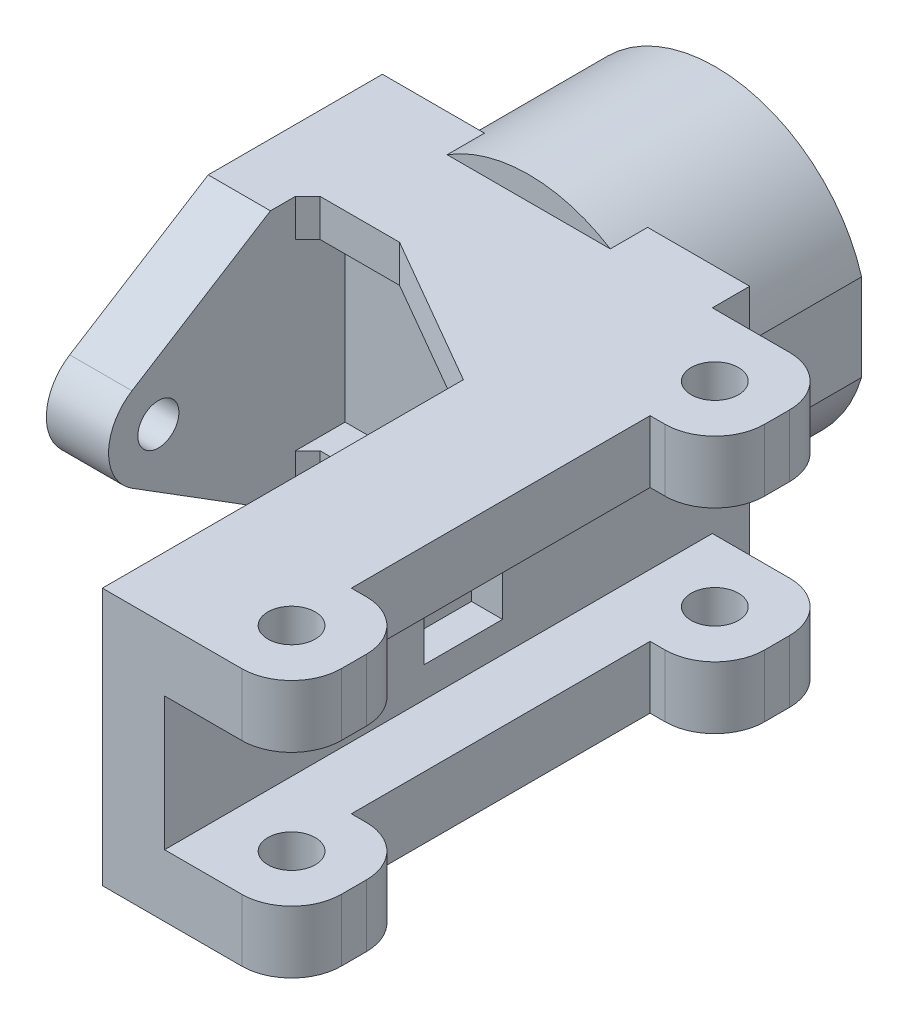
SolidWorks part; units mm, degrees
ref_plane "正面(Front)" through (0, 0, 0) normal (0, 0, 1) x (1, 0, 0)
ref_plane "平面(Top)" through (0, 0, 0) normal (0, 1, 0) x (1, 0, 0)
ref_plane "右側面(Right)" through (0, 0, 0) normal (1, 0, 0) x (0, 0, -1)
sketch "ｽｹｯﾁ1" plane through (0, 0, 0) normal (0, 0, 1) x (1, 0, 0)
  circle A0 centre (0, 0) radius 6.325
  dimension "D1" = 12.65
extrude "ﾎﾞｽ - 押し出し1" add sketch "ｽｹｯﾁ1" against normal blind 15
sketch "ｽｹｯﾁ2" plane through (0, 0, 0) normal (0, 0, 1) x (1, 0, 0)
  line L1 (-14.75, 10.35) -> (14.75, 10.35)
  line L2 (-14.75, 10.35) -> (-14.75, -10.35)
  line L3 (-14.75, -10.35) -> (14.75, -10.35)
  line L4 (14.75, 10.35) -> (14.75, -10.35)
  line L5 (-14.75, 10.35) -> (14.75, -10.35) construction
  line L6 (-14.75, -10.35) -> (14.75, 10.35) construction
  point P0 (0, 0)
  dimension "D1" = 20.7
  dimension "D2" = 29.5
extrude "ﾎﾞｽ - 押し出し2" add sketch "ｽｹｯﾁ2" along normal blind 5
sketch "ｽｹｯﾁ3" plane through (14.75, 0, 0) normal (1, 0, 0) x (0, 0, -1)
  line L0 (0, 0) -> (-31.0876, 0) construction
  line L1 (-5, 10.35) -> (-44, 10.35)
  line L3 (-44, 10.35) -> (-44, -10.35)
  line L6 (-5, -10.35) -> (-44, -10.35)
  line L7 (-5, 10.35) -> (-5, -10.35)
  circle A0 centre (-20, 0) radius 1.65
  dimension "D2" = 15
  dimension "D4" = 3.3
  dimension "D1" = 39
extrude "ﾎﾞｽ - 押し出し3" add sketch "ｽｹｯﾁ3" against normal blind 5
sketch "ｽｹｯﾁ4" plane through (14.75, 0, 0) normal (1, 0, 0) x (0, 0, -1)
  line L1 (0, 10.35) -> (-10, 10.35)
  line L2 (0, 10.35) -> (0, 5.35)
  line L3 (0, 5.35) -> (-10, 5.35)
  line L4 (-10, 10.35) -> (-10, 5.35)
  line L5 (0, -10.35) -> (-10, -10.35)
  line L6 (0, -10.35) -> (0, -5.35)
  line L7 (0, -5.35) -> (-10, -5.35)
  line L8 (-10, -10.35) -> (-10, -5.35)
  line L9 (-44, 10.35) -> (-34, 10.35)
  line L10 (-44, 10.35) -> (-44, 5.35)
  line L11 (-44, 5.35) -> (-34, 5.35)
  line L12 (-34, 10.35) -> (-34, 5.35)
  line L13 (-44, -10.35) -> (-34, -10.35)
  line L14 (-44, -10.35) -> (-44, -5.35)
  line L15 (-44, -5.35) -> (-34, -5.35)
  line L16 (-34, -10.35) -> (-34, -5.35)
  dimension "D1" = 5
  dimension "D2" = 5
  dimension "D3" = 10
  dimension "D4" = 10
extrude "ﾎﾞｽ - 押し出し4" add sketch "ｽｹｯﾁ4" along normal blind 10.2
sketch "ｽｹｯﾁ5" plane through (0, -10.35, 0) normal (0, -1, 0) x (1, 0, 0)
  line L4 (24.95, 5) -> (5.2641, 5) construction
  line L5 (24.95, 10) -> (24.95, 0) construction
  line L6 (24.95, 39) -> (4.1235, 39) construction
  line L7 (24.95, 44) -> (24.95, 34) construction
  circle A0 centre (19.95, 5) radius 1.9
  circle A2 centre (19.95, 39) radius 1.9
  dimension "D1" = 3.8
  dimension "D2" = 5
extrude "ｶｯﾄ - 押し出し1" cut sketch "ｽｹｯﾁ5" against normal through all
fillet "ﾌｨﾚｯﾄ1" radius 4 8 edges at (24.95, 7.85, 10) (24.95, 7.85, 0) (24.95, -7.85, 0) (24.95, -7.85, 10) (24.95, -7.85, 34) (24.95, 7.85, 34) (24.95, 7.85, 44) (24.95, -7.85, 44)
sketch "ｽｹｯﾁ8" plane through (14.75, 0, 0) normal (1, 0, 0) x (0, 0, -1)
  line L1 (-34, 10.35) -> (-10, 10.35)
  line L2 (-34, 10.35) -> (-34, 5.35)
  line L3 (-34, 5.35) -> (-10, 5.35)
  line L4 (-10, 10.35) -> (-10, 5.35)
  line L5 (-34, -5.35) -> (-10, -5.35)
  line L6 (-34, -5.35) -> (-34, -10.35)
  line L7 (-34, -10.35) -> (-10, -10.35)
  line L8 (-10, -5.35) -> (-10, -10.35)
extrude "ﾎﾞｽ - 押し出し6" add sketch "ｽｹｯﾁ8" along normal blind 5
sketch "ｽｹｯﾁ9" plane through (-14.75, 0, 0) normal (-1, 0, 0) x (0, 0, 1)
  line L0 (0, 0) -> (29.5336, 0) construction
  line L1 (5, 10.35) -> (11, 10.35)
  line L2 (5, 10.35) -> (44, 10.35) construction
  line L3 (11, 10.35) -> (22.1218, 3.3909)
  line L4 (11, -10.35) -> (22.1218, -3.3909)
  line L5 (5, -10.35) -> (11, -10.35)
  line L6 (5, -10.35) -> (5, 10.35)
  arc A0 (22.1218, 3.3909) -> (22.1218, -3.3909) centre (20, 0) cw
  circle A2 centre (20, 0) radius 1.65 construction
  circle A3 centre (20, 0) radius 1.65
  dimension "D1" = 4
  dimension "D3" = 3.3
  dimension "D2" = 6
extrude "ﾎﾞｽ - 押し出し7" add sketch "ｽｹｯﾁ9" against normal blind 5
sketch "ｽｹｯﾁ6" plane through (0, -10.35, 0) normal (0, -1, 0) x (1, 0, 0)
  line L3 (-9.75, 5) -> (9.75, 5) construction
  line L8 (9.75, 44) -> (9.75, 5) construction
  line L9 (-9.75, 5) -> (9.75, 5)
  line L10 (9.75, 5) -> (9.75, 15)
  line L11 (-9.75, 5) -> (9.75, 5) construction
  line L12 (-9.75, 5) -> (-9.75, 8)
  line L13 (-9.75, 5) -> (-9.75, 11) construction
  line L15 (-9.75, 8) -> (-2.3744, 8)
  line L16 (-2.3744, 8) -> (9.75, 15)
  dimension "D1" = 30
  dimension "D2" = 10
extrude "ﾎﾞｽ - 押し出し5" add sketch "ｽｹｯﾁ6" against normal blind 3
mirror "ﾐﾗｰ1" about plane through (0, 0, 0) normal (0, 1, 0) of "ﾎﾞｽ - 押し出し5"
chamfer "面取り1" [suppressed] distance 1 angle 45
chamfer "面取り2" distance 1 angle 45 2 edges at (-9.75, 8.85, 8) (-9.75, -8.85, 8)
sketch "ｽｹｯﾁ10" plane through (14.75, 0, 0) normal (1, 0, 0) x (0, 0, -1)
  line L1 (-23.15, 2.9) -> (-16.85, 2.9)
  line L2 (-23.15, 2.9) -> (-23.15, -2.9)
  line L3 (-23.15, -2.9) -> (-16.85, -2.9)
  line L4 (-16.85, 2.9) -> (-16.85, -2.9)
  line L5 (-23.15, 2.9) -> (-16.85, -2.9) construction
  line L6 (-23.15, -2.9) -> (-16.85, 2.9) construction
  point P0 (-20, 0)
  dimension "D1" = 5.8
  dimension "D2" = 6.3
extrude "ｶｯﾄ - 押し出し2" cut sketch "ｽｹｯﾁ10" against normal blind 2.5
sketch "ｽｹｯﾁ11" plane through (0, 0, 0) normal (1, 0, 0) x (0, 0, -1)
  line L0 (0, 0) -> (15, 0) construction
  line L1 (15, -6.325) -> (15, 6.325) construction
  line L2 (0, -6.325) -> (0, 6.325) construction
  circle A0 centre (7.5, 0) radius 1.65
  dimension "D1" = 3.3
  dimension "D2" = 7.5
extrude "ｶｯﾄ - 押し出し3" cut sketch "ｽｹｯﾁ11" against normal through all both and the other way through all
chamfer "面取り3" distance 1 angle 45 1 edges at (6.325, 0, -15)
sketch "ｽｹｯﾁ12" plane through (0, 10.35, 0) normal (0, 1, 0) x (1, 0, 0)
  line L0 (-20.8566, 0) -> (30.6219, 0)
extrude "ｶｯﾄ - 押し出し4" cut sketch "ｽｹｯﾁ12" against normal through all and the other way through all
sketch "ｽｹｯﾁ13" plane through (0, 0, 0) normal (0, 0, -1) x (-1, 0, 0)
  circle A0 centre (0, 0) radius 9.25
  circle A1 centre (0, 0) radius 12.25
  dimension "D1" = 18.5
  dimension "D2" = 3
extrude "ﾎﾞｽ - 押し出し8" add sketch "ｽｹｯﾁ13" along normal blind 15
sketch "ｽｹｯﾁ14" plane through (0, 0, 0) normal (1, 0, 0) x (0, 0, -1)
  line L0 (0, 0) -> (21.1695, 0) construction
  line L1 (0, -5.35) -> (0, 5.35) construction
  circle A0 centre (7.5, 0) radius 1.65
  point P4 (6.0711, -0.7588)
  dimension "D1" = 3.3
  dimension "D2" = 7.5
extrude "ｶｯﾄ - 押し出し5" cut sketch "ｽｹｯﾁ14" against normal through all both and the other way through all
sketch "ｽｹｯﾁ15" plane through (0, 0, -15) normal (0, 0, -1) x (-1, 0, 0)
  line L0 (-11.7394, 3.5) -> (-11.7394, -3.5)
  line L1 (-11.7394, -3.5) -> (-15.8764, -3.5)
  line L2 (-15.8764, -3.5) -> (-15.8764, 3.5)
  line L3 (-15.8764, 3.5) -> (-11.7394, 3.5)
  line L4 (0, 0) -> (0, 13.6834) construction
  line L5 (15.8764, -3.5) -> (15.8764, 3.5)
  line L6 (11.7394, -3.5) -> (15.8764, -3.5)
  line L7 (11.7394, 3.5) -> (11.7394, -3.5)
  line L8 (15.8764, 3.5) -> (11.7394, 3.5)
  circle A0 centre (0, 0) radius 12.25 construction
  arc A1 (-6.5529, 10.35) -> (-6.5529, -10.35) centre (0, 0) ccw construction
  dimension "D1" = 7
extrude "ｶｯﾄ - 押し出し6" cut sketch "ｽｹｯﾁ15" against normal up to surface (15 mm away) up to face at (16.5129, 0, 0)
sketch "ｽｹｯﾁ16" plane through (0, 0, 0) normal (0, 0, -1) x (-1, 0, 0)
  line L0 (0, 0) -> (0, 15.5048) construction
  line L1 (-11.7394, 3.5) -> (-11.7394, -3.5)
  line L2 (-14.75, 10.35) -> (-6.5529, 10.35)
  line L3 (-14.75, -10.35) -> (-14.75, 10.35)
  line L4 (6.5529, -10.35) -> (14.75, -10.35)
  line L6 (6.5529, -10.35) -> (14.75, -10.35)
  line L7 (11.7394, 3.5) -> (11.7394, -3.5)
  line L11 (11.7394, 3.5) -> (11.7394, -3.5)
  line L12 (-6.5529, -10.35) -> (-14.75, -10.35)
  line L13 (-6.5529, -10.35) -> (-20.95, -10.35) construction
  line L14 (-20.95, 10.35) -> (-6.5529, 10.35) construction
  line L18 (14.75, -10.35) -> (14.75, 10.35)
  line L20 (14.75, -10.35) -> (14.75, 10.35)
  line L21 (14.75, 10.35) -> (6.5529, 10.35)
  line L22 (14.75, 10.35) -> (6.5529, 10.35)
  arc A0 (-6.5529, -10.35) -> (-11.7394, -3.5) centre (0, 0) cw
  arc A1 (-11.7394, 3.5) -> (-6.5529, 10.35) centre (0, 0) cw
  arc A2 (11.7394, 3.5) -> (6.5529, 10.35) centre (0, 0) ccw
  arc A3 (6.5529, -10.35) -> (11.7394, -3.5) centre (0, 0) ccw
  arc A4 (11.7394, 3.5) -> (6.5529, 10.35) centre (0, 0) ccw
  arc A5 (6.5529, -10.35) -> (11.7394, -3.5) centre (0, 0) ccw
  point P1 (-14.75, -10.35)
  point P17 (-14.75, 10.35)
  dimension "D1" = 0
extrude "ﾎﾞｽ - 押し出し9" add sketch "ｽｹｯﾁ16" along normal blind 3
